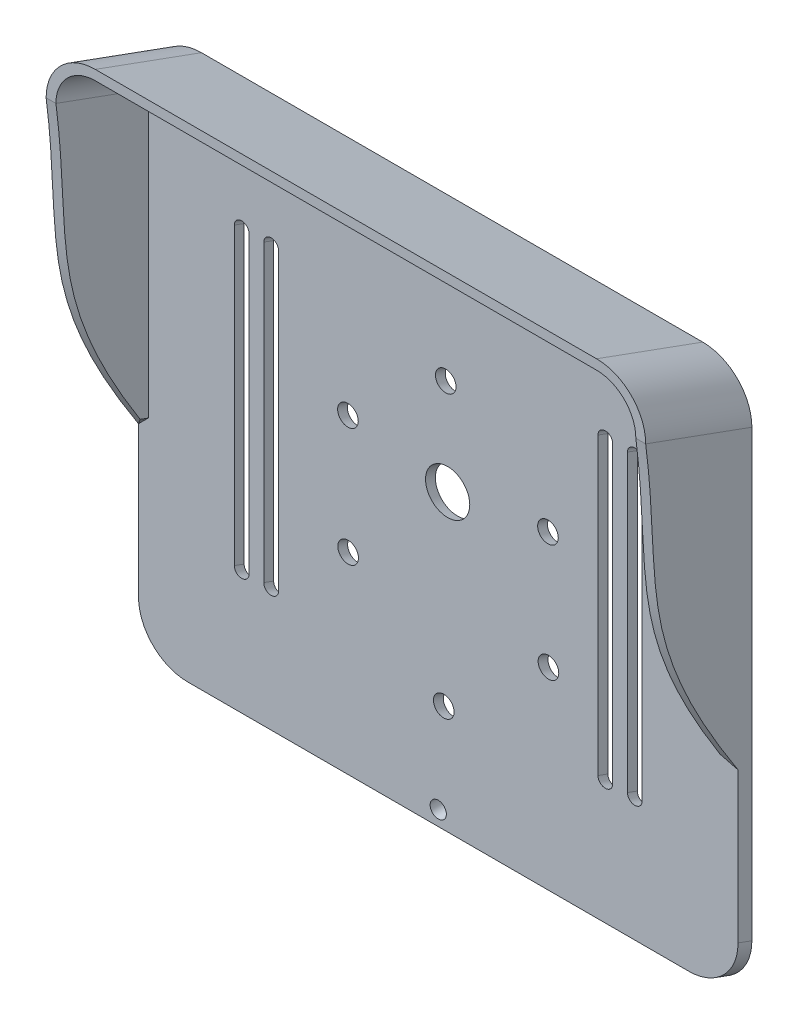
SolidWorks part; units mm, degrees
ref_plane "Alzado" through (0, 0, 0) normal (0, 0, 1) x (1, 0, 0)
ref_plane "Planta" through (0, 0, 0) normal (0, 1, 0) x (1, 0, 0)
ref_plane "Vista lateral" through (0, 0, 0) normal (1, 0, 0) x (0, 0, -1)
sketch "angulo_extrucion" plane through (0, 0, 0) normal (1, 0, 0) x (0, 0, -1)
  line L0 (0, 0) -> (18.895, -6.8772) construction
  line L1 (0, 0) -> (18.895, 0) construction
  line L2 (18.895, 0) -> (18.895, -6.8772) construction
  dimension "D1" = 20
sketch "Croquis1" plane through (0, 0, 0) normal (0, 0, 1) x (1, 0, 0)
  line L0 (-44.6, -48.85) -> (-44.6, -55.25) construction
  line L1 (-44.6, 48.85) -> (44.6, 48.85)
  line L2 (-54.6, 38.85) -> (-54.6, 33.85)
  line L3 (-44.6, -48.85) -> (44.6, -48.85)
  line L4 (54.6, 33.85) -> (54.6, -38.85)
  line L5 (-54.6, 48.85) -> (54.6, -48.85) construction
  line L6 (-54.6, -48.85) -> (54.6, 48.85) construction
  line L7 (51, -55.25) -> (-51, -55.25)
  line L8 (61, -45.25) -> (61, 38.85)
  line L9 (51, 55.25) -> (-51, 55.25)
  line L10 (-61, -45.25) -> (-61, 38.85)
  line L11 (61, -55.25) -> (-61, 55.25) construction
  line L12 (61, 55.25) -> (-61, -55.25) construction
  line L13 (-54.6, -38.85) -> (-61, -38.85) construction
  line L14 (-54.6, 38.85) -> (54.6, 38.85) construction
  line L15 (0, 55.25) -> (0, 38.85) construction
  line L16 (-61, 38.85) -> (-57.9, 38.85) construction
  line L17 (57.9, 38.85) -> (61, 38.85) construction
  line L18 (61, 38.85) -> (61, 45.25)
  line L19 (-61, 38.85) -> (-61, 45.25)
  line L20 (57.9, 38.85) -> (57.9, 33.85) construction
  line L21 (57.9, 33.85) -> (54.6, 33.85) construction
  line L22 (54.6, 38.85) -> (54.6, 33.85)
  line L23 (54.6, 38.85) -> (57.9, 38.85) construction
  line L24 (-54.6, 38.85) -> (-54.6, 33.85) construction
  line L25 (-57.9, 33.85) -> (-54.6, 33.85) construction
  line L26 (-57.9, 38.85) -> (-57.9, 33.85) construction
  line L27 (-57.9, 38.85) -> (-54.6, 38.85) construction
  line L28 (-54.6, 33.85) -> (-54.6, -38.85)
  arc A0 (-44.6, 48.85) -> (-54.6, 38.85) centre (-44.6, 38.85) ccw
  arc A1 (44.6, 48.85) -> (54.6, 38.85) centre (44.6, 38.85) cw
  arc A2 (44.6, -48.85) -> (54.6, -38.85) centre (44.6, -38.85) ccw
  arc A3 (-54.6, -38.85) -> (-44.6, -48.85) centre (-44.6, -38.85) ccw
  arc A4 (51, -55.25) -> (61, -45.25) centre (51, -45.25) ccw
  arc A5 (61, 45.25) -> (51, 55.25) centre (51, 45.25) ccw
  arc A6 (-51, -55.25) -> (-61, -45.25) centre (-51, -45.25) cw
  arc A7 (-51, 55.25) -> (-61, 45.25) centre (-51, 45.25) ccw
  point P0 (0, 0)
  point P17 (0, 0)
  dimension "D1" = 10
  dimension "D4" = 10
  dimension "D2" = 122
  dimension "D3" = 110.5
  dimension "D5" = 6.4
  dimension "D6" = 5
  dimension "D7" = 3.3
extrude "Saliente-Extruir1" add sketch "Croquis1" along direction (0, -0.342, -0.9397) on the side of the normal blind 3 contours L28 A3 L3 A2 L4 L22 A1 L1 A0 L2 | L9 A7 L19 L10 A6 L7 A4 L8 L18 A5 A3 L28 L2 A0 L1 A1 L22 L4 A2 L3 region at (0, 0, 0) region at (0, -53.604, 0)
extrude "Saliente-Extruir2" add sketch "Croquis1<3>" along direction (0, -0.342, -0.9397) on the side against the normal blind 3 contours L28 A3 L3 A2 L4 L22 A1 L1 A0 L2 region at (0, 0, 0)
sketch "Croquis1<3>" plane through (0, 0, 0) normal (0, 0, 1) x (1, 0, 0) same geometry as "Croquis1"
shell "Vaciado1" thickness 2 removed face at (0, -1.0261, -2.8191)
sketch "Croquis2" plane through (0, 0, 2.8191) normal (0, 0, 1) x (1, 0, 0)
  line L0 (-61, 1.0261) -> (61, 1.0261) construction
  line L1 (61, -44.2239) -> (61, 46.2761) construction
  line L2 (0, -54.2239) -> (0, 56.2761) construction
  line L3 (51, 56.2761) -> (-51, 56.2761) construction
  line L4 (-18.3772, 9.0743) -> (1.5228, 25.0743) construction
  line L5 (1.5228, 25.0743) -> (22.3228, 8.8743) construction
  line L6 (22.3228, 8.8743) -> (22.4228, -14.9257) construction
  line L7 (22.4228, -14.9257) -> (1.1228, -32.4257) construction
  line L8 (1.1228, -32.4257) -> (-18.3372, -15.0257) construction
  line L9 (-18.3372, -15.0257) -> (-18.3772, 9.0743) construction
  line L10 (0, 1.0261) -> (1.9103, 5.696) construction
  line L11 (-40, -28.9739) -> (-40, 31.0261) construction
  line L12 (-41.5, -28.9739) -> (-41.5, 31.0261)
  line L13 (-38.5, -28.9739) -> (-38.5, 31.0261)
  line L14 (-32.5, -28.9739) -> (-32.5, 31.0261)
  line L15 (-35.5, -28.9739) -> (-35.5, 31.0261)
  line L16 (-34, -28.9739) -> (-34, 31.0261) construction
  line L17 (-38.5, -28.9739) -> (-32.5, -28.9739) construction
  line L18 (40, -28.9739) -> (40, 31.0261) construction
  line L19 (41.5, -28.9739) -> (41.5, 31.0261)
  line L20 (38.5, -28.9739) -> (38.5, 31.0261)
  line L21 (34, -28.9739) -> (34, 31.0261) construction
  line L22 (35.5, -28.9739) -> (35.5, 31.0261)
  line L23 (32.5, -28.9739) -> (32.5, 31.0261)
  circle A0 centre (1.5228, 25.0743) radius 2.1
  circle A1 centre (22.3228, 8.8743) radius 2.1
  circle A2 centre (22.4228, -14.9257) radius 2.1
  circle A3 centre (1.1228, -32.4257) radius 2.1
  circle A4 centre (-18.3372, -15.0257) radius 2.1
  circle A5 centre (-18.3772, 9.0743) radius 2.1
  circle A6 centre (1.9103, 5.696) radius 4.5
  arc A7 (-41.5, -28.9739) -> (-38.5, -28.9739) centre (-40, -28.9739) ccw
  arc A8 (-38.5, 31.0261) -> (-41.5, 31.0261) centre (-40, 31.0261) ccw
  arc A9 (-35.5, -28.9739) -> (-32.5, -28.9739) centre (-34, -28.9739) ccw
  arc A10 (-32.5, 31.0261) -> (-35.5, 31.0261) centre (-34, 31.0261) ccw
  arc A11 (41.5, -28.9739) -> (38.5, -28.9739) centre (40, -28.9739) cw
  arc A12 (38.5, 31.0261) -> (41.5, 31.0261) centre (40, 31.0261) cw
  arc A13 (35.5, -28.9739) -> (32.5, -28.9739) centre (34, -28.9739) cw
  arc A14 (32.5, 31.0261) -> (35.5, 31.0261) centre (34, 31.0261) cw
  point P6 (0, 1.0261)
  point P10 (0, 1.0261)
  point P13 (0, 1.0261)
  point P37 (-40, 1.0261)
  point P43 (-34, 1.0261)
  point P51 (40, 1.0261)
  point P58 (34, 1.0261)
  dimension "D1" = 4.2
  dimension "D2" = 9
  dimension "D3" = 60
  dimension "D4" = 3
  dimension "D5" = 40
  dimension "D7" = 6
  dimension "D8" = 8.0483
  dimension "D9" = 24.0483
  dimension "D10" = 4.6699
  dimension "D11" = 7.8483
  dimension "D12" = 16.0517
  dimension "D13" = 33.4517
  dimension "D14" = 15.9517
  dimension "D15" = 1.9103
  dimension "D16" = 22.3228
  dimension "D17" = 22.4228
  dimension "D18" = 1.1228
  dimension "D19" = 18.3372
  dimension "D20" = 18.3772
  dimension "D21" = 1.5228
  dimension "D6" = 2
extrude "agujeros_frontales" cut sketch "Croquis2" along direction (0, -0.342, -0.9397) on the side against the normal up to next (2 mm away)
sketch "Croquis4" plane through (0, 0, 2.8191) normal (0, 0, 1) x (1, 0, 0)
  line L1 (51, 56.2761) -> (-51, 56.2761)
  line L2 (-61, 46.2761) -> (-61, -11.7239)
  line L3 (-61, -44.2239) -> (-61, 46.2761) construction
  line L4 (-61, -13.7239) -> (-59, -11.7239)
  line L5 (-59, -11.7239) -> (-59, 46.2761)
  line L6 (0, 56.2761) -> (0, 54.2761)
  line L7 (51, 54.2761) -> (-51, 54.2761)
  line L8 (-51, 54.2761) -> (-51, 56.2761) construction
  line L9 (-59, 46.2761) -> (-61, 46.2761) construction
  line L10 (-59, -11.7239) -> (-61, -11.7239) construction
  line L11 (61, 46.2761) -> (61, -13.7239)
  line L12 (61, -13.7239) -> (59, -11.7239)
  line L13 (59, -11.7239) -> (59, 46.2761)
  line L14 (-61, -11.7239) -> (-61, -13.7239)
  arc A1 (-51, 56.2761) -> (-61, 46.2761) centre (-51, 46.2761) ccw construction
  arc A3 (-51, 56.2761) -> (-61, 46.2761) centre (-51, 46.2761) ccw
  arc A4 (-59, 46.2761) -> (-51, 54.2761) centre (-51, 46.2761) cw
  arc A5 (51, 56.2761) -> (61, 46.2761) centre (51, 46.2761) cw
  arc A6 (59, 46.2761) -> (51, 54.2761) centre (51, 46.2761) ccw
  line M41 (51, 56.2761) -> (-51, 56.2761)
  arc M42 (-51, 56.2761) -> (-61, 46.2761) centre (-51, 46.2761) ccw
  line M43 (-61, 46.2761) -> (-61, -44.2239)
  line M47 (61, -44.2239) -> (61, 46.2761)
  arc M48 (61, 46.2761) -> (51, 56.2761) centre (51, 46.2761) ccw
  dimension "D1" = 45
  dimension "D2" = 2
  dimension "D3" = 70
extrude "Saliente-Extruir3" add sketch "Croquis4" along direction (0, -0.342, -0.9397) on the side of the normal blind 20 contours A6 L13 L12 L6 L7 M47 M48 M41 | L5 A4 L7 L6 L1 L4 M42 M43 region at (57.4145, 52.6906, 2.8191) region at (-0.9285, 55.2761, 2.8191)
sketch "Croquis5" plane through (61, 0, 0) normal (1, 0, 0) x (0, 0, -1)
  line L0 (-21.6129, 53.1165) -> (-21.6129, -13.7239)
  line L1 (-21.6129, -13.7239) -> (-2.8191, -13.7239)
  line L2 (-21.6129, 63.1165) -> (-21.6129, 53.1165) construction
  spline S0 degree 3 poles (-21.6129, 53.1165) (-18.1928, 26.402) (-24.2022, 19.2503) (-2.8191, -13.7239) knots 0.107845 0.107845 0.107845 0.107845 1 1 1 1
  spline S1 degree 2 poles (-21.6129, 63.1165) (-22.2331, 57.9604) (-21.6129, 53.1165) knots 0 0 0 0.107845 0.107845 0.107845 construction
extrude "Cortar-Extruir2" cut sketch "Croquis5" against normal through all both and the other way through all
sketch "Croquis6" plane through (0, 0, 2.8191) normal (0, 0, 1) x (1, 0, 0)
  line L0 (0, 0) -> (0, -48.2239) construction
  line L1 (60.1652, -48.2239) -> (-60.1652, -48.2239) construction
  line L2 (0, -48.2239) -> (0, -54.2239) construction
  line L3 (51, -54.2239) -> (-51, -54.2239) construction
  circle A0 centre (0, -51.2239) radius 1.65
  arc A1 (51, -54.2239) -> (61, -44.2239) centre (51, -44.2239) ccw construction
  arc A2 (-61, -44.2239) -> (-51, -54.2239) centre (-51, -44.2239) ccw construction
  point P8 (60.3154, -47.8604)
  point P12 (-60.3154, -47.8604)
  point P16 (0, -54.2239)
  point P19 (0, -51.071)
  point P20 (0, 0)
  dimension "D1" = 3.3
  dimension "D2" = 6
extrude "Cortar-Extruir3" cut sketch "Croquis6" against normal up to next
